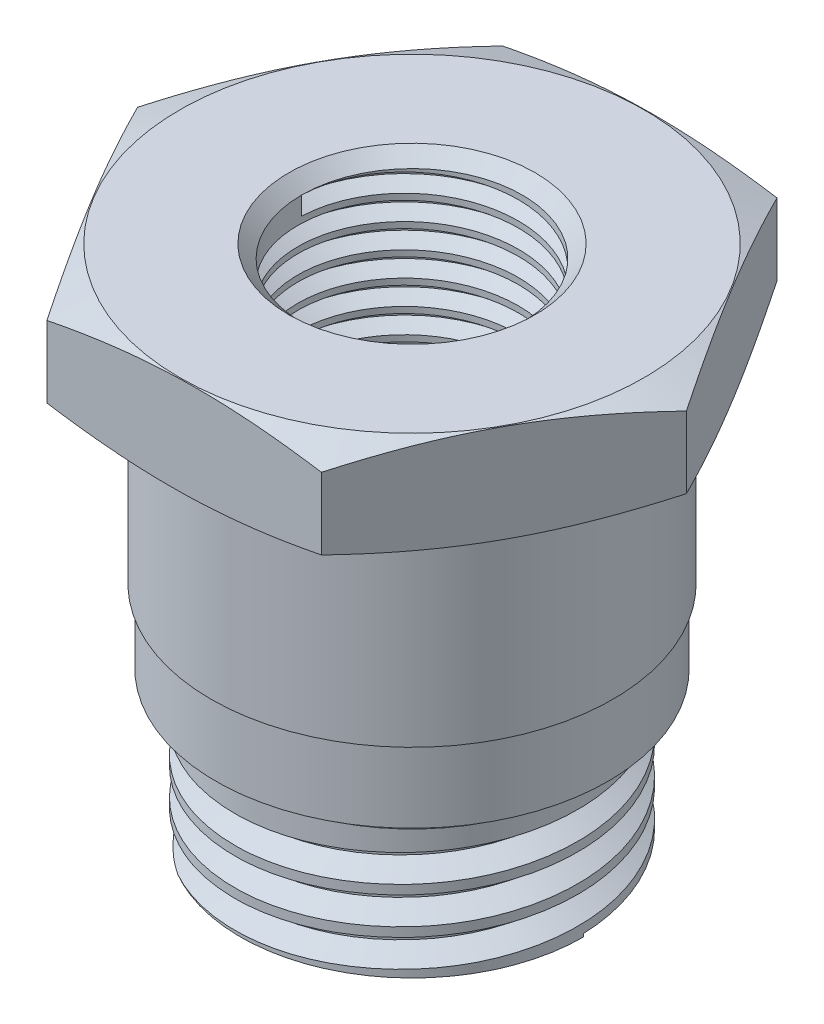
SolidWorks part; units mm, degrees
material "AISI 1020"
ref_plane "Plano superior" through (0, 0, 0) normal (0, 0, 1) x (1, 0, 0)
ref_plane "Plano frontal" through (0, 0, 0) normal (0, 1, 0) x (1, 0, 0)
ref_plane "Plano direito" through (0, 0, 0) normal (1, 0, 0) x (0, 0, -1)
sketch "Esboço1" plane through (0, 0, 0) normal (0, 1, 0) x (1, 0, 0)
  line L1 (5.2831, 9.6137) -> (-5.6841, 9.3821)
  line L2 (-5.6841, 9.3821) -> (-10.9672, -0.2315)
  line L3 (-10.9672, -0.2315) -> (-5.2831, -9.6137)
  line L4 (-5.2831, -9.6137) -> (5.6841, -9.3821)
  line L5 (5.6841, -9.3821) -> (10.9672, 0.2315)
  line L6 (10.9672, 0.2315) -> (5.2831, 9.6137)
  circle A0 centre (0, 0) radius 9.5 construction
  dimension "D1" = 19
extrude "Ressalto-extrusão1" add sketch "Esboço1" along normal blind 4
sketch "Esboço4" plane through (0, 0, 0) normal (0, -1, 0) x (1, 0, 0)
  circle A0 centre (0, 0) radius 9.5
extrude "Corte-extrusão2" cut sketch "Esboço4" against normal blind 13 draft 70 flip side to cut
sketch "Esboço5" plane through (0, 4, 0) normal (0, 1, 0) x (1, 0, 0)
  circle A0 centre (0, 0) radius 9.4723
extrude "Corte-extrusão3" cut sketch "Esboço5" against normal blind 13 draft 70 flip side to cut
sketch "Esboço6" plane through (0, 0, 0) normal (0, -1, 0) x (1, 0, 0)
  circle A0 centre (0, 0) radius 8.2
  arc A1 (0.2005, 9.4979) -> (-8.1252, 4.9226) centre (0, 0) ccw construction
  dimension "D1" = 16.4
extrude "Ressalto-extrusão2" add sketch "Esboço6" along normal blind 8
sketch "Esboço7" plane through (0, -8, 0) normal (0, -1, 0) x (1, 0, 0)
  circle A0 centre (0, 0) radius 8
  dimension "D1" = 16
extrude "Ressalto-extrusão3" add sketch "Esboço7" along normal blind 3
sketch "Esboço8" plane through (0, -11, 0) normal (0, -1, 0) x (1, 0, 0)
  circle A0 centre (0, 0) radius 7
  dimension "D1" = 14
extrude "Ressalto-extrusão4" add sketch "Esboço8" along normal blind 6 contours A0
cosmetic thread "Representação de rosca1" parameters "D2"=11.797
sketch "Esboço9" plane through (0, -17, 0) normal (0, -1, 0) x (1, 0, 0)
  circle A1 centre (0, 0) radius 5.2
  dimension "D1" = 10.4
extrude "Corte-extrusão4" cut sketch "Esboço9" against normal blind 14
hole_wizard "Furo roscado de M10x1.01" positions "Esboço11" profile "Esboço12" tap size "M10x1.0" standard "DIN" end condition up to next
sketch "Esboço11" plane through (0, 4, 0) normal (0, 1, 0) x (1, 0, 0)
  point P0 (0, 0)
sketch "Esboço12" plane through (0, 4, 0) normal (1, 0, 0) x (0, 0, 1)
  line L0 (0, 0) -> (0, 7)
  line L1 (0, 7) -> (4.5, 7)
  line L2 (4.5, 7) -> (4.5, 0.525)
  line L3 (4.5, 0.525) -> (5.025, 0)
  line L5 (5.025, 0) -> (0, 0)
  line L6 (-4.5, 0.525) -> (-5.025, 0) construction
  line L11 (0, -6.35) -> (0, 107.95) construction
  dimension "Thru Tap Drill Dia." = 9
  dimension "Thru Tap Drill Depth" = 7
  dimension "Near C'Sink Dia." = 10.05
  dimension "Near C'Sink Angle" = 90
cosmetic thread "Rosca de furo1" parameters "D2"=10
thread "Rosca1" pitch 1 method cut profile "Perfil da rosca1" start angle 0, offset 0, length 0, pitch 1, diameter 9
ref_plane "Plano1" through (-4.5, 3.475, 0) normal (0, 0, 1) x (-1, 0, 0)
sketch "Perfil da rosca1" plane through (-4.5, 3.475, 0) normal (0, 0, 1) x (-1, 0, 0)
  line L0 (0, 0) -> (0, 1) construction
  line L1 (0, 0) -> (0.5413, 0.3125)
  line L2 (0.5413, 0.3125) -> (0.5413, 0.4375)
  line L3 (0.5413, 0.4375) -> (0, 0.75)
  line L4 (0.5413, 0.375) -> (0, 0.375) construction
  line L11 (0, 0) -> (0, 0.75)
  point P2 (0, 0)
  dimension "Pitch" = 1
  dimension "Profile_Angle" = 60
  dimension "Profile_Land" = 0.125
  dimension "Profile_Height" = 0.5413
other "Mover face1" face at (0, -17, -5.2) offset 2 parameters "D1"=2
sketch "Esboço15" plane through (0, -19, 0) normal (0, -1, 0) x (1, 0, 0)
  circle A0 centre (0, 0) radius 9.5
extrude "Corte-extrusão6" cut sketch "Esboço15" against normal blind 2
sketch "Esboço19" plane through (0, 0, 0) normal (1, 0, 0) x (0, 0, -1)
  line L0 (0, 0) -> (0, -28.3099) construction
  line L1 (-7, -11) -> (7, -11) construction
  line L2 (-6.3549, -11) -> (-7.8648, -11)
  line L3 (-6.3549, -11) -> (-6.3549, -11.736)
  line L4 (-6.3549, -11.736) -> (-7.8648, -11.736)
  line L5 (-7.8648, -11) -> (-7.8648, -11.736)
revolve "Corte-Revolução1" cut sketch "Esboço19" angle 360 about L0
thread "Rosca2" pitch 1.5 method cut profile "Perfil da rosca2" start angle 0, offset 1, length 0, pitch 1.5, diameter 14
ref_plane "Plano2" through (7, -18, 0) normal (0, 0, -1) x (-1, 0, 0)
sketch "Perfil da rosca2" plane through (7, -18, 0) normal (0, 0, -1) x (-1, 0, 0)
  line L0 (0, 0) -> (0, 1.5) construction
  line L1 (0, 0) -> (0.8119, 0.4687)
  line L2 (0.8119, 0.4687) -> (0.8119, 0.6562)
  line L3 (0.8119, 0.6562) -> (0, 1.125)
  line L4 (0.8119, 0.5625) -> (0, 0.5625) construction
  line L11 (0, 0) -> (0, 1.125)
  point P2 (0, 0)
  dimension "Pitch" = 1.5
  dimension "Profile_Angle" = 60
  dimension "Profile_Land" = 0.1875
  dimension "Profile_Height" = 0.8119
ref_axis "Eixo1" through (0, -18.584, 0) along (0, 1, 0)
